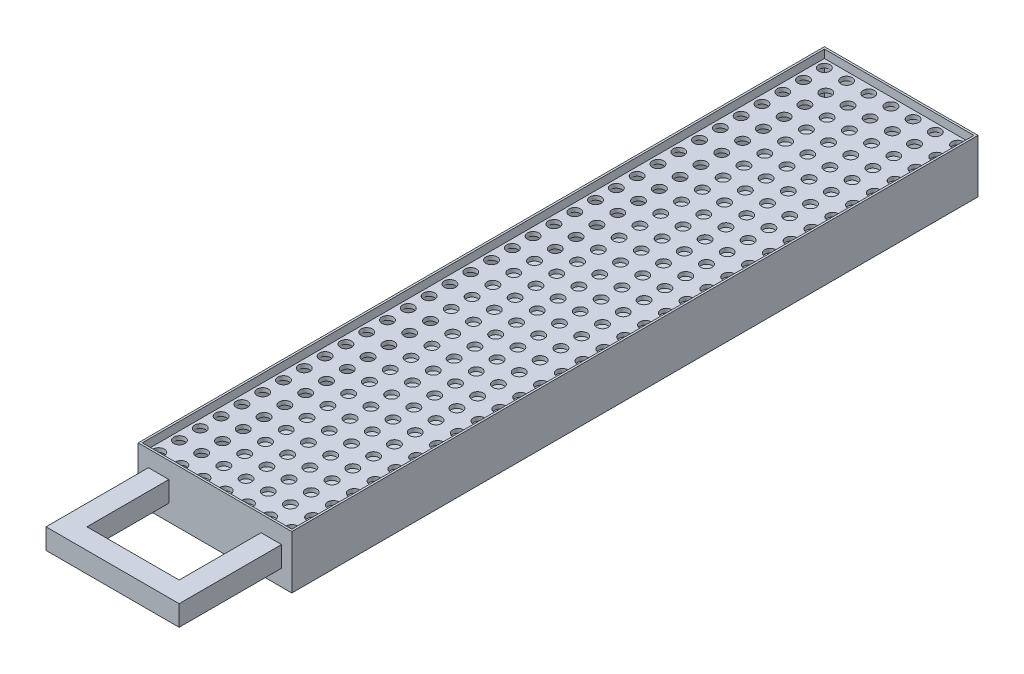
SolidWorks part; units mm, degrees
ref_plane "Alzado" through (0, 0, 0) normal (0, 0, 1) x (1, 0, 0)
ref_plane "Planta" through (0, 0, 0) normal (0, 1, 0) x (1, 0, 0)
ref_plane "Vista lateral" through (0, 0, 0) normal (1, 0, 0) x (0, 0, -1)
sketch "Croquis1" plane through (0, 0, 0) normal (0, 1, 0) x (1, 0, 0)
  line L1 (37.5, 167.5) -> (-37.5, 167.5)
  line L2 (37.5, 167.5) -> (37.5, -167.5)
  line L3 (37.5, -167.5) -> (-37.5, -167.5)
  line L4 (-37.5, 167.5) -> (-37.5, -167.5)
  line L5 (37.5, 167.5) -> (-37.5, -167.5) construction
  line L6 (37.5, -167.5) -> (-37.5, 167.5) construction
  point P0 (0, 0)
extrude "Saliente-Extruir1" add sketch "Croquis1" along normal blind 20 contours L4 L3 L2 L1
sketch "Croquis2" plane through (0, 20, 0) normal (0, 1, 0) x (1, 0, 0)
  line L0 (37.5, 167.5) -> (-37.5, 167.5) construction
  line L1 (37.5, 167.5) -> (37.5, -167.5) construction
  line L2 (-37.5, 167.5) -> (-37.5, -167.5) construction
  line L3 (37.5, -167.5) -> (-37.5, -167.5) construction
  circle A0 centre (32.5, 162.5) radius 2.75
  circle A1 centre (32.5, 152.3437) radius 2.75
  circle A2 centre (32.5, 142.1875) radius 2.75
  circle A3 centre (32.5, 132.0312) radius 2.75
  circle A4 centre (32.5, 121.875) radius 2.75
  circle A5 centre (32.5, 111.7187) radius 2.75
  circle A6 centre (32.5, 101.5625) radius 2.75
  circle A7 centre (32.5, 91.4062) radius 2.75
  circle A8 centre (32.5, 81.25) radius 2.75
  circle A9 centre (32.5, 71.0937) radius 2.75
  circle A10 centre (32.5, 60.9375) radius 2.75
  circle A11 centre (32.5, 50.7812) radius 2.75
  circle A12 centre (32.5, 40.625) radius 2.75
  circle A13 centre (32.5, 30.4687) radius 2.75
  circle A14 centre (32.5, 20.3125) radius 2.75
  circle A15 centre (32.5, 10.1562) radius 2.75
  circle A16 centre (32.5, 0) radius 2.75
  circle A17 centre (32.5, -10.1563) radius 2.75
  circle A18 centre (32.5, -20.3125) radius 2.75
  circle A19 centre (32.5, -30.4688) radius 2.75
  circle A20 centre (32.5, -40.625) radius 2.75
  circle A21 centre (32.5, -50.7813) radius 2.75
  circle A22 centre (32.5, -60.9375) radius 2.75
  circle A23 centre (32.5, -71.0938) radius 2.75
  circle A24 centre (32.5, -81.25) radius 2.75
  circle A25 centre (32.5, -91.4063) radius 2.75
  circle A26 centre (32.5, -101.5625) radius 2.75
  circle A27 centre (32.5, -111.7188) radius 2.75
  circle A28 centre (32.5, -121.875) radius 2.75
  circle A29 centre (32.5, -132.0313) radius 2.75
  circle A30 centre (32.5, -142.1875) radius 2.75
  circle A31 centre (32.5, -152.3438) radius 2.75
  circle A32 centre (32.5, -162.5) radius 2.75
  circle A33 centre (21.6667, 152.3437) radius 2.75
  circle A34 centre (21.6667, 142.1875) radius 2.75
  circle A35 centre (21.6667, 132.0312) radius 2.75
  circle A36 centre (21.6667, 121.875) radius 2.75
  circle A37 centre (21.6667, 111.7187) radius 2.75
  circle A38 centre (21.6667, 101.5625) radius 2.75
  circle A39 centre (21.6667, 91.4062) radius 2.75
  circle A40 centre (21.6667, 81.25) radius 2.75
  circle A41 centre (21.6667, 71.0937) radius 2.75
  circle A42 centre (21.6667, 60.9375) radius 2.75
  circle A43 centre (21.6667, 50.7812) radius 2.75
  circle A44 centre (21.6667, 40.625) radius 2.75
  circle A45 centre (21.6667, 30.4687) radius 2.75
  circle A46 centre (21.6667, 20.3125) radius 2.75
  circle A47 centre (21.6667, 10.1562) radius 2.75
  circle A48 centre (21.6667, 0) radius 2.75
  circle A49 centre (21.6667, -10.1563) radius 2.75
  circle A50 centre (21.6667, -20.3125) radius 2.75
  circle A51 centre (21.6667, -30.4688) radius 2.75
  circle A52 centre (21.6667, -40.625) radius 2.75
  circle A53 centre (21.6667, -50.7813) radius 2.75
  circle A54 centre (21.6667, -60.9375) radius 2.75
  circle A55 centre (21.6667, -71.0938) radius 2.75
  circle A56 centre (21.6667, -81.25) radius 2.75
  circle A57 centre (21.6667, -91.4063) radius 2.75
  circle A58 centre (21.6667, -101.5625) radius 2.75
  circle A59 centre (21.6667, -111.7188) radius 2.75
  circle A60 centre (21.6667, -121.875) radius 2.75
  circle A61 centre (21.6667, -132.0313) radius 2.75
  circle A62 centre (21.6667, -142.1875) radius 2.75
  circle A63 centre (21.6667, -152.3438) radius 2.75
  circle A64 centre (21.6667, -162.5) radius 2.75
  circle A65 centre (10.8333, 152.3437) radius 2.75
  circle A66 centre (10.8333, 142.1875) radius 2.75
  circle A67 centre (10.8333, 132.0312) radius 2.75
  circle A68 centre (10.8333, 121.875) radius 2.75
  circle A69 centre (10.8333, 111.7187) radius 2.75
  circle A70 centre (10.8333, 101.5625) radius 2.75
  circle A71 centre (10.8333, 91.4062) radius 2.75
  circle A72 centre (10.8333, 81.25) radius 2.75
  circle A73 centre (10.8333, 71.0937) radius 2.75
  circle A74 centre (10.8333, 60.9375) radius 2.75
  circle A75 centre (10.8333, 50.7812) radius 2.75
  circle A76 centre (10.8333, 40.625) radius 2.75
  circle A77 centre (10.8333, 30.4687) radius 2.75
  circle A78 centre (10.8333, 20.3125) radius 2.75
  circle A79 centre (10.8333, 10.1562) radius 2.75
  circle A80 centre (10.8333, 0) radius 2.75
  circle A81 centre (10.8333, -10.1563) radius 2.75
  circle A82 centre (10.8333, -20.3125) radius 2.75
  circle A83 centre (10.8333, -30.4688) radius 2.75
  circle A84 centre (10.8333, -40.625) radius 2.75
  circle A85 centre (10.8333, -50.7813) radius 2.75
  circle A86 centre (10.8333, -60.9375) radius 2.75
  circle A87 centre (10.8333, -71.0938) radius 2.75
  circle A88 centre (10.8333, -81.25) radius 2.75
  circle A89 centre (10.8333, -91.4063) radius 2.75
  circle A90 centre (10.8333, -101.5625) radius 2.75
  circle A91 centre (10.8333, -111.7188) radius 2.75
  circle A92 centre (10.8333, -121.875) radius 2.75
  circle A93 centre (10.8333, -132.0313) radius 2.75
  circle A94 centre (10.8333, -142.1875) radius 2.75
  circle A95 centre (10.8333, -152.3438) radius 2.75
  circle A96 centre (10.8333, -162.5) radius 2.75
  circle A97 centre (0, 152.3437) radius 2.75
  circle A98 centre (0, 142.1875) radius 2.75
  circle A99 centre (0, 132.0312) radius 2.75
  circle A100 centre (0, 121.875) radius 2.75
  circle A101 centre (0, 111.7187) radius 2.75
  circle A102 centre (0, 101.5625) radius 2.75
  circle A103 centre (0, 91.4062) radius 2.75
  circle A104 centre (0, 81.25) radius 2.75
  circle A105 centre (0, 71.0937) radius 2.75
  circle A106 centre (0, 60.9375) radius 2.75
  circle A107 centre (0, 50.7812) radius 2.75
  circle A108 centre (0, 40.625) radius 2.75
  circle A109 centre (0, 30.4687) radius 2.75
  circle A110 centre (0, 20.3125) radius 2.75
  circle A111 centre (0, 10.1562) radius 2.75
  circle A112 centre (0, 0) radius 2.75
  circle A113 centre (0, -10.1563) radius 2.75
  circle A114 centre (0, -20.3125) radius 2.75
  circle A115 centre (0, -30.4688) radius 2.75
  circle A116 centre (0, -40.625) radius 2.75
  circle A117 centre (0, -50.7813) radius 2.75
  circle A118 centre (0, -60.9375) radius 2.75
  circle A119 centre (0, -71.0938) radius 2.75
  circle A120 centre (0, -81.25) radius 2.75
  circle A121 centre (0, -91.4063) radius 2.75
  circle A122 centre (0, -101.5625) radius 2.75
  circle A123 centre (0, -111.7188) radius 2.75
  circle A124 centre (0, -121.875) radius 2.75
  circle A125 centre (0, -132.0313) radius 2.75
  circle A126 centre (0, -142.1875) radius 2.75
  circle A127 centre (0, -152.3438) radius 2.75
  circle A128 centre (0, -162.5) radius 2.75
  circle A129 centre (-10.8333, 152.3437) radius 2.75
  circle A130 centre (-10.8333, 142.1875) radius 2.75
  circle A131 centre (-10.8333, 132.0312) radius 2.75
  circle A132 centre (-10.8333, 121.875) radius 2.75
  circle A133 centre (-10.8333, 111.7187) radius 2.75
  circle A134 centre (-10.8333, 101.5625) radius 2.75
  circle A135 centre (-10.8333, 91.4062) radius 2.75
  circle A136 centre (-10.8333, 81.25) radius 2.75
  circle A137 centre (-10.8333, 71.0937) radius 2.75
  circle A138 centre (-10.8333, 60.9375) radius 2.75
  circle A139 centre (-10.8333, 50.7812) radius 2.75
  circle A140 centre (-10.8333, 40.625) radius 2.75
  circle A141 centre (-10.8333, 30.4687) radius 2.75
  circle A142 centre (-10.8333, 20.3125) radius 2.75
  circle A143 centre (-10.8333, 10.1562) radius 2.75
  circle A144 centre (-10.8333, 0) radius 2.75
  circle A145 centre (-10.8333, -10.1563) radius 2.75
  circle A146 centre (-10.8333, -20.3125) radius 2.75
  circle A147 centre (-10.8333, -30.4688) radius 2.75
  circle A148 centre (-10.8333, -40.625) radius 2.75
  circle A149 centre (-10.8333, -50.7813) radius 2.75
  circle A150 centre (-10.8333, -60.9375) radius 2.75
  circle A151 centre (-10.8333, -71.0938) radius 2.75
  circle A152 centre (-10.8333, -81.25) radius 2.75
  circle A153 centre (-10.8333, -91.4063) radius 2.75
  circle A154 centre (-10.8333, -101.5625) radius 2.75
  circle A155 centre (-10.8333, -111.7188) radius 2.75
  circle A156 centre (-10.8333, -121.875) radius 2.75
  circle A157 centre (-10.8333, -132.0313) radius 2.75
  circle A158 centre (-10.8333, -142.1875) radius 2.75
  circle A159 centre (-10.8333, -152.3438) radius 2.75
  circle A160 centre (-10.8333, -162.5) radius 2.75
  circle A161 centre (-21.6667, 152.3437) radius 2.75
  circle A162 centre (-21.6667, 142.1875) radius 2.75
  circle A163 centre (-21.6667, 132.0312) radius 2.75
  circle A164 centre (-21.6667, 121.875) radius 2.75
  circle A165 centre (-21.6667, 111.7187) radius 2.75
  circle A166 centre (-21.6667, 101.5625) radius 2.75
  circle A167 centre (-21.6667, 91.4062) radius 2.75
  circle A168 centre (-21.6667, 81.25) radius 2.75
  circle A169 centre (-21.6667, 71.0937) radius 2.75
  circle A170 centre (-21.6667, 60.9375) radius 2.75
  circle A171 centre (-21.6667, 50.7812) radius 2.75
  circle A172 centre (-21.6667, 40.625) radius 2.75
  circle A173 centre (-21.6667, 30.4687) radius 2.75
  circle A174 centre (-21.6667, 20.3125) radius 2.75
  circle A175 centre (-21.6667, 10.1562) radius 2.75
  circle A176 centre (-21.6667, 0) radius 2.75
  circle A177 centre (-21.6667, -10.1563) radius 2.75
  circle A178 centre (-21.6667, -20.3125) radius 2.75
  circle A179 centre (-21.6667, -30.4688) radius 2.75
  circle A180 centre (-21.6667, -40.625) radius 2.75
  circle A181 centre (-21.6667, -50.7813) radius 2.75
  circle A182 centre (-21.6667, -60.9375) radius 2.75
  circle A183 centre (-21.6667, -71.0938) radius 2.75
  circle A184 centre (-21.6667, -81.25) radius 2.75
  circle A185 centre (-21.6667, -91.4063) radius 2.75
  circle A186 centre (-21.6667, -101.5625) radius 2.75
  circle A187 centre (-21.6667, -111.7188) radius 2.75
  circle A188 centre (-21.6667, -121.875) radius 2.75
  circle A189 centre (-21.6667, -132.0313) radius 2.75
  circle A190 centre (-21.6667, -142.1875) radius 2.75
  circle A191 centre (-21.6667, -152.3438) radius 2.75
  circle A192 centre (-21.6667, -162.5) radius 2.75
  circle A193 centre (-32.5, 152.3437) radius 2.75
  circle A194 centre (-32.5, 142.1875) radius 2.75
  circle A195 centre (-32.5, 132.0312) radius 2.75
  circle A196 centre (-32.5, 121.875) radius 2.75
  circle A197 centre (-32.5, 111.7187) radius 2.75
  circle A198 centre (-32.5, 101.5625) radius 2.75
  circle A199 centre (-32.5, 91.4062) radius 2.75
  circle A200 centre (-32.5, 81.25) radius 2.75
  circle A201 centre (-32.5, 71.0937) radius 2.75
  circle A202 centre (-32.5, 60.9375) radius 2.75
  circle A203 centre (-32.5, 50.7812) radius 2.75
  circle A204 centre (-32.5, 40.625) radius 2.75
  circle A205 centre (-32.5, 30.4687) radius 2.75
  circle A206 centre (-32.5, 20.3125) radius 2.75
  circle A207 centre (-32.5, 10.1562) radius 2.75
  circle A208 centre (-32.5, 0) radius 2.75
  circle A209 centre (-32.5, -10.1563) radius 2.75
  circle A210 centre (-32.5, -20.3125) radius 2.75
  circle A211 centre (-32.5, -30.4688) radius 2.75
  circle A212 centre (-32.5, -40.625) radius 2.75
  circle A213 centre (-32.5, -50.7813) radius 2.75
  circle A214 centre (-32.5, -60.9375) radius 2.75
  circle A215 centre (-32.5, -71.0938) radius 2.75
  circle A216 centre (-32.5, -81.25) radius 2.75
  circle A217 centre (-32.5, -91.4063) radius 2.75
  circle A218 centre (-32.5, -101.5625) radius 2.75
  circle A219 centre (-32.5, -111.7188) radius 2.75
  circle A220 centre (-32.5, -121.875) radius 2.75
  circle A221 centre (-32.5, -132.0313) radius 2.75
  circle A222 centre (-32.5, -142.1875) radius 2.75
  circle A223 centre (-32.5, -152.3438) radius 2.75
  circle A224 centre (-32.5, -162.5) radius 2.75
  circle A225 centre (21.6667, 162.5) radius 2.75
  circle A226 centre (10.8333, 162.5) radius 2.75
  circle A227 centre (0, 162.5) radius 2.75
  circle A228 centre (-10.8333, 162.5) radius 2.75
  circle A229 centre (-21.6667, 162.5) radius 2.75
  circle A230 centre (-32.5, 162.5) radius 2.75
  dimension "D1" = 5
  dimension "D2" = 5
  dimension "D5" = 5
  dimension "D6" = 5
  dimension "D3" = 33
  dimension "D4" = 7
shell "Vaciado1" thickness 2 removed face at (0, 0, 0)
extrude "Cortar-Extruir1" cut sketch "Croquis2" against normal up to next (2 mm away)
sketch "Croquis3" plane through (35.5, 0, 0) normal (-1, 0, 0) x (0, 0, 1)
  line L0 (-165.5, 18) -> (-165.5, 0) construction
  line L5 (-23, 8) -> (22.2559, 8)
  line L6 (-23, 8) -> (-23, 3)
  line L7 (-23, 3) -> (22.2559, 3)
  line L8 (22.2559, 8) -> (22.2559, 3)
  line L9 (-23, 8) -> (22.2559, 3) construction
  line L10 (-23, 3) -> (22.2559, 8) construction
  line L25 (-165.5, 0) -> (165.5, 0) construction
  point P0 (-0.372, 5.5)
  point P14 (-165.5, 18)
  dimension "D1" = 3
  dimension "D2" = 5
  dimension "D3" = 142.5
extrude "Saliente-Extruir3" add sketch "Croquis3" along normal up to next
sketch "Croquis4" plane through (0, 0, 0) normal (0, -1, 0) x (1, 0, 0)
  line L1 (-37.5, 167.5) -> (37.5, 167.5)
  line L2 (-37.5, 167.5) -> (-37.5, -167.5)
  line L3 (-37.5, -167.5) -> (37.5, -167.5)
  line L4 (37.5, 167.5) -> (37.5, -167.5)
  line L5 (-37.5, 167.5) -> (37.5, -167.5) construction
  line L6 (-37.5, -167.5) -> (37.5, 167.5) construction
  point P4 (0, 0)
extrude "Saliente-Extruir5" add sketch "Croquis4" along normal blind 2
sketch "Croquis6" plane through (0, 20, 0) normal (0, 1, 0) x (1, 0, 0)
  line L1 (-37.5, 167.5) -> (37.5, 167.5)
  line L2 (-37.5, 167.5) -> (-37.5, -167.5)
  line L3 (-37.5, -167.5) -> (37.5, -167.5)
  line L4 (37.5, 167.5) -> (37.5, -167.5)
  line L5 (-37.5, 167.5) -> (37.5, -167.5) construction
  line L6 (-37.5, -167.5) -> (37.5, 167.5) construction
  line L11 (37.5, -167.5) -> (-37.5, -167.5) construction
  line L12 (-37.5, 167.5) -> (-37.5, -167.5) construction
  point P4 (0, 0)
extrude "Saliente-Extruir6" add sketch "Croquis6" along normal blind 4
sketch "Croquis9" plane through (0, 24, 0) normal (0, 1, 0) x (1, 0, 0)
  line L0 (-37.5, 167.5) -> (-37.5, -167.5) construction
  line L1 (-36.5, 166.5) -> (36.5, 166.5)
  line L2 (-36.5, 166.5) -> (-36.5, -166.5)
  line L3 (-36.5, -166.5) -> (36.5, -166.5)
  line L4 (36.5, 166.5) -> (36.5, -166.5)
  line L5 (-36.5, 166.5) -> (36.5, -166.5) construction
  line L6 (-36.5, -166.5) -> (36.5, 166.5) construction
  line L7 (-37.5, -167.5) -> (37.5, -167.5) construction
  line L8 (37.5, -167.5) -> (37.5, 167.5) construction
  line L9 (37.5, 167.5) -> (-37.5, 167.5) construction
  point P4 (0, 0)
  dimension "D1" = 1
  dimension "D2" = 1
  dimension "D3" = 1
  dimension "D4" = 1
extrude "Cortar-Extruir2" cut sketch "Croquis9" against normal blind 4
sketch "Croquis10" plane through (0, -2, 0) normal (0, -1, 0) x (1, 0, 0)
  line L0 (37.5, 167.5) -> (-37.5, 167.5) construction
  line L1 (-37.5, 167.5) -> (-37.5, -167.5) construction
  circle A0 centre (-29.5, 159.5) radius 5
  dimension "D1" = 10
  dimension "D2" = 8
  dimension "D3" = 8
extrude "Cortar-Extruir3" cut sketch "Croquis10" against normal up to next
sketch "Croquis11" plane through (0, 0, 167.5) normal (0, 0, 1) x (1, 0, 0)
  line L0 (-37.5, 24) -> (-37.5, -2) construction
  line L1 (-32.5, 16) -> (-22.5, 16)
  line L2 (-32.5, 16) -> (-32.5, 6)
  line L3 (-32.5, 6) -> (-22.5, 6)
  line L4 (-22.5, 16) -> (-22.5, 6)
  line L5 (-32.5, 16) -> (-22.5, 6) construction
  line L6 (-32.5, 6) -> (-22.5, 16) construction
  line L8 (-37.5, 24) -> (37.5, 24) construction
  line L10 (37.5, -2) -> (-37.5, -2) construction
  line L11 (0, 24) -> (0, -2)
  line L12 (32.5, 6) -> (22.5, 6)
  line L13 (22.5, 16) -> (22.5, 6)
  line L14 (32.5, 16) -> (22.5, 16)
  line L15 (32.5, 16) -> (32.5, 6)
  point P4 (-27.5, 11)
  dimension "D1" = 5
  dimension "D2" = 10
  dimension "D3" = 8
extrude "Saliente-Extruir7" add sketch "Croquis11" along normal blind 50 contours L15 L14 L13 L12 | L3 L4 L1 L2 region at (27.5, 11, 167.5)
sketch "Croquis12" plane through (-22.5, 0, 0) normal (1, 0, 0) x (0, 0, -1)
  line L0 (-207.5, 16) -> (-207.5, 6)
  line L1 (-217.5, 16) -> (-167.5, 16) construction
  line L2 (-217.5, 6) -> (-167.5, 6) construction
  line L3 (-217.5, 16) -> (-217.5, 6) construction
  line L8 (-167.5, 6) -> (-167.5, 16)
  line L9 (-167.5, 16) -> (-217.5, 16)
  line L10 (-217.5, 16) -> (-217.5, 6)
  line L11 (-217.5, 6) -> (-167.5, 6)
  line L13 (-207.5, 16) -> (-217.5, 16)
  line L14 (-217.5, 16) -> (-217.5, 6)
  line L15 (-217.5, 6) -> (-207.5, 6)
  dimension "D1" = 10
  dimension "D2" = 0
extrude "Saliente-Extruir8" add sketch "Croquis12" along normal up to next
sketch "Croquis13" plane through (0, -2, 0) normal (0, -1, 0) x (1, 0, 0)
  line L4 (9.9507, -67.5) -> (9.9507, 67.5) construction
  line L12 (37.5, 167.5) -> (-37.5, 167.5) construction
  line L13 (-37.5, -167.5) -> (37.5, -167.5) construction
  line L16 (-10, -67.5) -> (-10, 67.5) construction
  line L17 (-10, -67.5) -> (9.9507, -67.5) construction
  line L18 (-10, 67.5) -> (9.9507, 67.5) construction
  line L19 (-37.5, 167.5) -> (-37.5, -167.5) construction
  line L20 (37.5, -167.5) -> (37.5, 167.5) construction
  text T0 "EituCher18" font "Century Gothic" height in points 72
  point P4 (0, 0)
  dimension "D1" = 135
  dimension "D2" = 100
  dimension "D3" = 100
  dimension "D4" = 19.9507
  dimension "D5" = 19.9507
  dimension "D6" = 27.5
  dimension "D7" = 27.5493
extrude "Cortar-Extruir4" cut sketch "Croquis13" against normal blind 0.2
